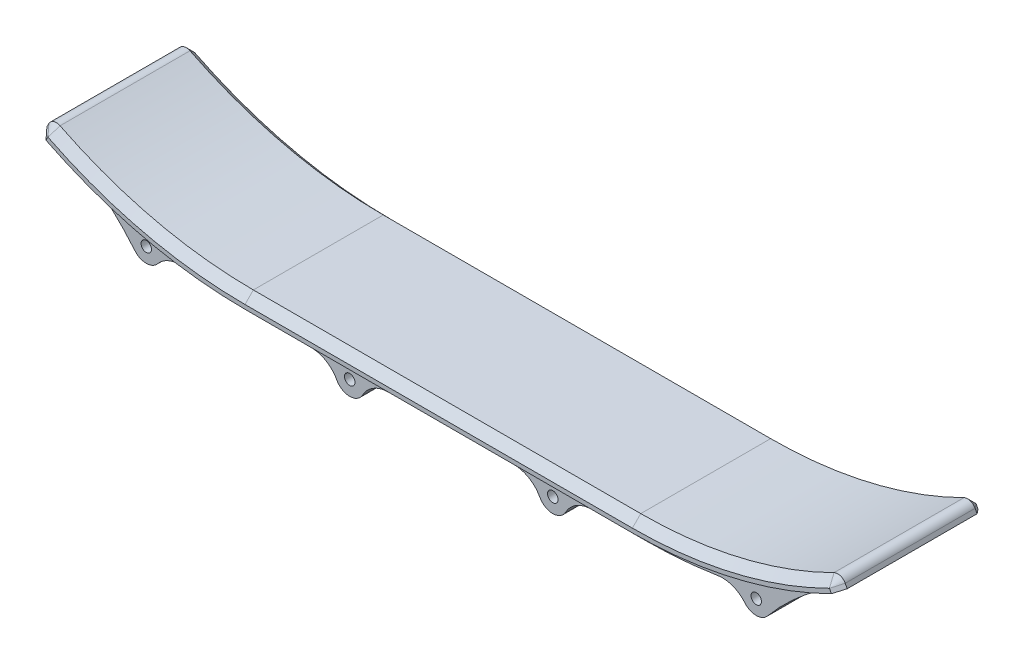
SolidWorks part; units mm, degrees
material "尼龙 101"
ref_plane "前视基准面" through (0, 0, 0) normal (0, 0, 1) x (1, 0, 0)
ref_plane "上视基准面" through (0, 0, 0) normal (0, 1, 0) x (1, 0, 0)
ref_plane "右视基准面" through (0, 0, 0) normal (1, 0, 0) x (0, 0, -1)
sketch "草图1" plane through (0, 0, 0) normal (0, 0, 1) x (1, 0, 0)
  line L0 (-71.2712, 30) -> (-163.7288, 30) construction
  line L1 (-71.2712, 33) -> (-163.7288, 33)
  line L2 (-71.2712, 25) -> (-163.7288, 25) construction
  line L3 (-22.4719, 43.0012) -> (-22, 42.0981)
  line L4 (-212.5281, 43.0012) -> (-213, 42.0981)
  line L5 (-71.2712, 27) -> (-163.7288, 27) construction
  line L6 (-71.2712, 27) -> (-84.0381, 27)
  line L8 (-117.5, 27) -> (-117.5, 44.4862) construction
  line L10 (-163.7288, 27) -> (-150.9619, 27)
  line L11 (-132.4957, 27) -> (-102.5043, 27)
  circle A0 centre (-44.7115, 28.213) radius 1.25
  circle A1 centre (-93.2712, 25) radius 1.25
  circle A2 centre (-141.7288, 25) radius 1.25
  circle A3 centre (-190.2885, 28.213) radius 1.25
  arc A4 (-22, 42.0981) -> (-71.2712, 30) centre (-71.2712, 136.381) cw construction
  arc A5 (-19.6842, 37.6667) -> (-71.2712, 25) centre (-71.2712, 136.381) cw construction
  arc A6 (-71.2712, 30) -> (-22, 42.0981) centre (-71.2712, 136.381) ccw construction
  arc A7 (-163.7288, 30) -> (-213, 42.0981) centre (-163.7288, 136.381) cw construction
  arc A8 (-25.137, 43.8647) -> (-71.2712, 33) centre (-71.2712, 136.381) cw
  arc A9 (-163.7288, 33) -> (-209.863, 43.8647) centre (-163.7288, 136.381) cw
  arc A10 (-163.7288, 25) -> (-215.3158, 37.6667) centre (-163.7288, 136.381) cw construction
  arc A11 (-23.3895, 44.7569) -> (-71.2712, 33) centre (-71.2712, 136.381) cw construction
  arc A12 (-25.137, 43.8647) -> (-22.4719, 43.0012) centre (-24.2445, 42.0749) cw
  arc A13 (-163.7288, 33) -> (-211.6105, 44.7569) centre (-163.7288, 136.381) cw construction
  arc A14 (-209.863, 43.8647) -> (-212.5281, 43.0012) centre (-210.7555, 42.0749) ccw
  arc A15 (-22, 42.0981) -> (-42.0262, 25.9683) centre (8.5018, -16.2686) ccw
  arc A16 (-90.1935, 23.3333) -> (-84.0381, 27) centre (-84.0381, 20) cw
  arc A17 (-42.0262, 25.9683) -> (-47.3973, 25.9687) centre (-44.7115, 28.213) cw
  arc A18 (-90.1935, 23.3333) -> (-96.3489, 23.3333) centre (-93.2712, 25) cw
  arc A19 (-213, 42.0981) -> (-192.9738, 25.9683) centre (-243.5018, -16.2686) cw
  arc A20 (-20.6105, 39.4393) -> (-71.2712, 27) centre (-71.2712, 136.381) cw construction
  arc A21 (-163.7288, 27) -> (-214.3895, 39.4393) centre (-163.7288, 136.381) cw construction
  arc A22 (-47.3973, 25.9687) -> (-53.8816, 28.3912) centre (-52.7688, 21.4802) ccw
  arc A23 (-53.8816, 28.3912) -> (-71.2712, 27) centre (-71.2712, 136.381) cw
  arc A24 (-96.3489, 23.3333) -> (-102.5043, 27) centre (-102.5043, 20) ccw
  arc A25 (-192.9738, 25.9683) -> (-187.6027, 25.9687) centre (-190.2885, 28.213) ccw
  arc A26 (-187.6027, 25.9687) -> (-181.1184, 28.3912) centre (-182.2312, 21.4802) cw
  arc A27 (-181.1184, 28.3912) -> (-163.7288, 27) centre (-163.7288, 136.381) ccw
  arc A28 (-144.8065, 23.3333) -> (-150.9619, 27) centre (-150.9619, 20) ccw
  arc A29 (-144.8065, 23.3333) -> (-138.6511, 23.3333) centre (-141.7288, 25) ccw
  arc A30 (-138.6511, 23.3333) -> (-132.4957, 27) centre (-132.4957, 20) cw
  point P54 (-117.5, 27)
  dimension "D3" = 2
  dimension "D4" = 3.5
  dimension "D5" = 3.5
  dimension "D6" = 2.5
  dimension "D7" = 2
  dimension "D8" = 7
  dimension "D1" = 3
  dimension "D2" = 5
extrude "凸台-拉伸1" add sketch "草图1" along normal blind 29
sketch "草图2" plane through (0, 0, 0) normal (0, 0, -1) x (-1, 0, 0)
  line L0 (163.7288, 30) -> (71.2712, 30) construction
  line L1 (163.7288, 30) -> (71.2712, 30)
  line L2 (212.5281, 43.0012) -> (213, 42.0981) construction
  line L3 (71.2712, 33) -> (163.7288, 33) construction
  line L4 (22, 42.0981) -> (22.4719, 43.0012) construction
  line L5 (212.5281, 43.0012) -> (213, 42.0981)
  line L6 (71.2712, 33) -> (163.7288, 33)
  line L7 (22, 42.0981) -> (22.4719, 43.0012)
  arc A0 (22, 42.0981) -> (71.2712, 30) centre (71.2712, 136.381) ccw construction
  arc A1 (163.7288, 30) -> (213, 42.0981) centre (163.7288, 136.381) ccw construction
  arc A2 (22, 42.0981) -> (71.2712, 30) centre (71.2712, 136.381) ccw
  arc A3 (163.7288, 30) -> (213, 42.0981) centre (163.7288, 136.381) ccw
  arc A4 (212.5281, 43.0012) -> (209.863, 43.8647) centre (210.7555, 42.0749) ccw construction
  arc A5 (163.7288, 33) -> (209.863, 43.8647) centre (163.7288, 136.381) ccw construction
  arc A6 (25.137, 43.8647) -> (71.2712, 33) centre (71.2712, 136.381) ccw construction
  arc A7 (25.137, 43.8647) -> (22.4719, 43.0012) centre (24.2445, 42.0749) ccw construction
  arc A8 (212.5281, 43.0012) -> (209.863, 43.8647) centre (210.7555, 42.0749) ccw
  arc A9 (163.7288, 33) -> (209.863, 43.8647) centre (163.7288, 136.381) ccw
  arc A10 (25.137, 43.8647) -> (71.2712, 33) centre (71.2712, 136.381) ccw
  arc A11 (25.137, 43.8647) -> (22.4719, 43.0012) centre (24.2445, 42.0749) ccw
extrude "凸台-拉伸2" add sketch "草图2" along normal blind 3 and the other way blind 32
chamfer "倒角1" distance 2 angle 45 14 edges at (-212.764, 42.5496, 32) (-22.236, 42.5496, 32) (-211.372, 43.9775, 32) (-23.628, 43.9775, 32) (-187.4269, 35.7528, 32) (-47.5731, 35.7528, 32) (-117.5, 33, 32) (-212.764, 42.5496, -3) (-22.236, 42.5496, -3) (-211.372, 43.9775, -3) (-23.628, 43.9775, -3) (-187.4269, 35.7528, -3) (-47.5731, 35.7528, -3) (-117.5, 33, -3)
